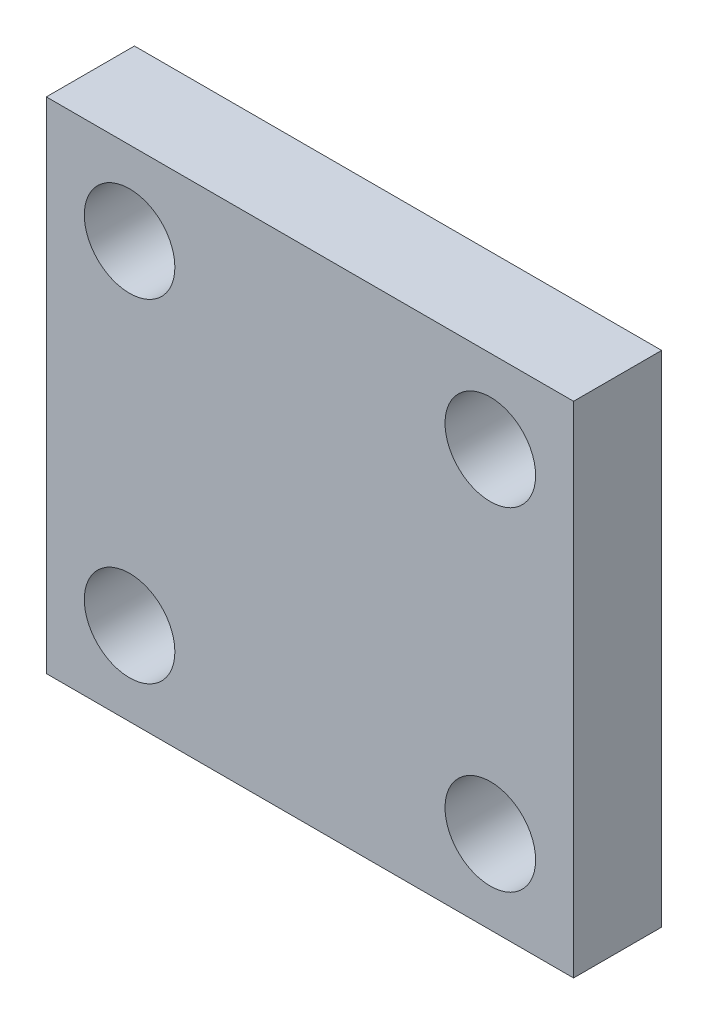
SolidWorks part; units mm, degrees
ref_plane "Front Plane" through (0, 0, 0) normal (0, 0, 1) x (1, 0, 0)
ref_plane "Top Plane" through (0, 0, 0) normal (0, 1, 0) x (1, 0, 0)
ref_plane "Right Plane" through (0, 0, 0) normal (1, 0, 0) x (0, 0, -1)
sketch "Sketch1" plane through (0, 0, 0) normal (0, 0, 1) x (1, 0, 0)
  line L1 (0, 0) -> (38, 0)
  line L2 (0, 0) -> (0, 36)
  line L3 (0, 36) -> (38, 36)
  line L4 (38, 0) -> (38, 36)
  dimension "D1" = 38
  dimension "D2" = 36
extrude "Boss-Extrude1" add sketch "Sketch1" along normal blind 6.35
sketch "Sketch3" plane through (0, 0, 6.35) normal (0, 0, 1) x (1, 0, 0)
  line L0 (6, 6) -> (0, 6) construction
  line L1 (0, 36) -> (0, 0) construction
  line L2 (6, 6) -> (6, 0) construction
  line L3 (0, 0) -> (38, 0) construction
  line L4 (19, 36) -> (19, 0) construction
  line L7 (38, 36) -> (0, 36) construction
  line L8 (0, 18) -> (38, 18) construction
  line L9 (0, 36) -> (0, 0) construction
  line L10 (38, 0) -> (38, 36) construction
  circle A0 centre (6, 6) radius 3 construction
  circle A1 centre (32, 6) radius 3 construction
  circle A2 centre (32, 30) radius 3 construction
  circle A3 centre (6, 30) radius 3 construction
  point P0 (6, 6)
  point P12 (32, 6)
  point P19 (6, 6)
  point P33 (32, 30)
  point P35 (6, 30)
  dimension "D1" = 6
  dimension "D2" = 26
  dimension "D3" = 24
hole_wizard "1/4 Clearance Hole1" positions "Sketch3" profile "Sketch6" hole size "1/4" standard "ANSI Inch" end condition through all
sketch "Sketch6" plane through (6, 30, 6.35) normal (1, 0, 0) x (0, -1, 0)
  line L0 (0, 0) -> (0, 6.35)
  line L1 (0, 6.35) -> (3.2639, 6.35)
  line L2 (3.2639, 6.35) -> (3.2639, 0)
  line L5 (3.2639, 0) -> (0, 0)
  line L11 (0, -6.35) -> (0, 107.95) construction
  dimension "Thru Hole Dia." = 6.5278
  dimension "Thru Hole Depth" = 6.35
